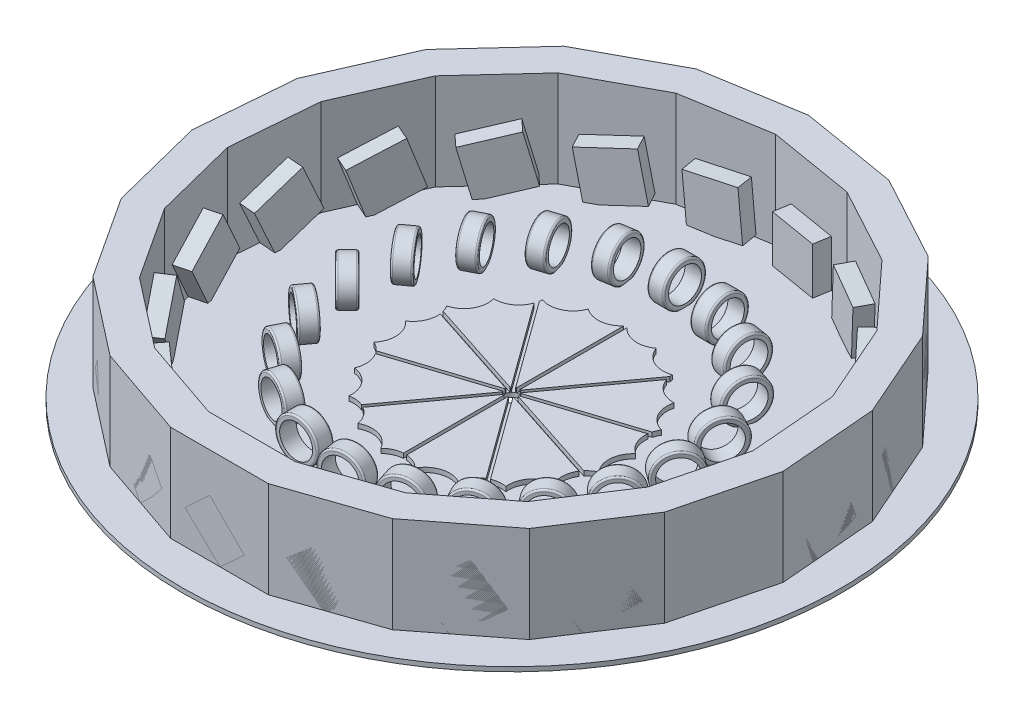
SolidWorks part; units mm, degrees
ref_plane "Front Plane" through (0, 0, 0) normal (0, 0, 1) x (1, 0, 0)
ref_plane "Top Plane" through (0, 0, 0) normal (0, 1, 0) x (1, 0, 0)
ref_plane "Right Plane" through (0, 0, 0) normal (1, 0, 0) x (0, 0, -1)
sketch "Sketch1" plane through (0, 0, 0) normal (0, 1, 0) x (1, 0, 0)
  circle A0 centre (0, 0) radius 100
  circle A1 centre (0, 0) radius 2
  dimension "D1" = 200
  dimension "D2" = 4
extrude "Base Platter" add sketch "Sketch1" along normal blind 0.75
sketch "Sketch2" plane through (0, 0.75, 0) normal (0, 1, 0) x (1, 0, 0)
  line L0 (0, 0) -> (0, 35) construction
  line L1 (0, 0) -> (10.3164, 33.445) construction
  line L2 (0, 0) -> (19.7162, 28.9184) construction
  line L3 (0, 0) -> (27.3641, 21.8221) construction
  line L4 (0, 0) -> (32.5806, 12.7869) construction
  line L5 (0, 0) -> (34.9021, 2.6156) construction
  line L6 (0, 0) -> (34.1225, -7.7882) construction
  line L7 (0, 0) -> (30.3109, -17.5) construction
  line L8 (0, 0) -> (23.806, -25.6568) construction
  line L9 (0, 0) -> (15.1859, -31.5339) construction
  line L10 (0, 0) -> (5.2165, -34.6091) construction
  line L11 (0, 0) -> (-5.2165, -34.6091) construction
  line L12 (0, 0) -> (-15.1859, -31.5339) construction
  line L13 (0, 0) -> (-23.806, -25.6568) construction
  line L14 (0, 0) -> (-30.3109, -17.5) construction
  line L15 (0, 0) -> (-34.1225, -7.7882) construction
  line L16 (0, 0) -> (-34.9021, 2.6156) construction
  line L17 (0, 0) -> (-32.5806, 12.7869) construction
  line L18 (0, 0) -> (-27.3641, 21.8221) construction
  line L19 (0, 0) -> (-19.7162, 28.9184) construction
  line L20 (0, 0) -> (-10.3164, 33.445) construction
  line L21 (0, 0) -> (4.4705, 29.665) construction
  line L22 (0, 0) -> (13.0158, 27.0294) construction
  line L23 (0, 0) -> (20.4046, 21.9921) construction
  line L24 (0, 0) -> (25.9804, 15.0006) construction
  line L25 (0, 0) -> (29.2477, 6.6764) construction
  line L26 (0, 0) -> (29.9162, -2.2412) construction
  line L27 (0, 0) -> (27.9265, -10.9595) construction
  line L28 (0, 0) -> (23.4554, -18.7041) construction
  line L29 (0, 0) -> (16.9002, -24.7867) construction
  line L30 (0, 0) -> (8.8434, -28.667) construction
  line L31 (0, 0) -> (0.0007, -30) construction
  line L32 (0, 0) -> (-8.8419, -28.6674) construction
  line L33 (0, 0) -> (-16.899, -24.7876) construction
  line L34 (0, 0) -> (-23.4545, -18.7053) construction
  line L35 (0, 0) -> (-27.9259, -10.9609) construction
  line L36 (0, 0) -> (-29.9161, -2.2426) construction
  line L37 (0, 0) -> (-29.248, 6.6749) construction
  line L38 (0, 0) -> (-25.9811, 14.9994) construction
  line L39 (0, 0) -> (-20.4057, 21.991) construction
  line L40 (0, 0) -> (-13.0172, 27.0287) construction
  line L41 (0, 0) -> (-4.472, 29.6648) construction
  line L42 (0, 0) -> (0, 59.7258) construction
  line L43 (34.5674, 11.7574) -> (-41.5171, -12.964)
  line L44 (-0.5, 36.5088) -> (0.5, 36.5088)
  line L45 (-0.5, 36.5088) -> (-0.5, -43.4912)
  line L46 (-0.5, -43.4912) -> (0.5, -43.4912)
  line L47 (0.5, 36.5088) -> (0.5, -43.4912)
  line L48 (34.8764, 10.8063) -> (-41.2081, -13.9151)
  line L49 (34.5674, 11.7574) -> (34.8764, 10.8063)
  line L50 (-41.5171, -12.964) -> (-41.2081, -13.9151)
  line L51 (21.8638, -29.2423) -> (-25.159, 35.479)
  line L52 (21.0548, -29.8301) -> (-25.968, 34.8913)
  line L53 (21.8638, -29.2423) -> (21.0548, -29.8301)
  line L54 (-25.159, 35.479) -> (-25.968, 34.8913)
  line L55 (-21.0548, -29.8301) -> (25.968, 34.8913)
  line L56 (-21.8638, -29.2423) -> (25.159, 35.479)
  line L57 (-21.0548, -29.8301) -> (-21.8638, -29.2423)
  line L58 (25.968, 34.8913) -> (25.159, 35.479)
  line L59 (-34.8764, 10.8063) -> (41.2081, -13.9151)
  line L60 (-34.5674, 11.7574) -> (41.5171, -12.964)
  line L61 (-34.8764, 10.8063) -> (-34.5674, 11.7574)
  line L62 (41.2081, -13.9151) -> (41.5171, -12.964)
  circle A0 centre (0, 0) radius 30 construction
  circle A1 centre (0, 0) radius 2 construction
  circle A2 centre (0, 0) radius 35 construction
  arc A3 (-19.7162, 28.9184) -> (-10.3164, 33.445) centre (-17.2797, 35.8816) ccw
  arc A4 (-10.3164, 33.445) -> (0, 35) centre (-5.9357, 39.3807) ccw
  arc A5 (0, 35) -> (10.3164, 33.445) centre (5.9357, 39.3807) ccw
  arc A6 (10.3164, 33.445) -> (19.7162, 28.9184) centre (17.2797, 35.8816) ccw
  arc A7 (19.7162, 28.9184) -> (27.3641, 21.8221) centre (27.0883, 29.1942) ccw
  arc A8 (27.3641, 21.8221) -> (32.5806, 12.7869) centre (34.4899, 19.9128) ccw
  arc A9 (32.5806, 12.7869) -> (34.9021, 2.6156) centre (38.827, 8.862) ccw
  arc A10 (34.9021, 2.6156) -> (34.1225, -7.7882) centre (39.7142, -2.9762) ccw
  arc A11 (34.1225, -7.7882) -> (30.3109, -17.5) centre (37.0726, -14.5499) ccw
  arc A12 (30.3109, -17.5) -> (23.806, -25.6568) centre (31.1369, -24.8308) ccw
  arc A13 (23.806, -25.6568) -> (15.1859, -31.5339) centre (22.4345, -32.9054) ccw
  arc A14 (15.1859, -31.5339) -> (5.2165, -34.6091) centre (11.7388, -38.0562) ccw
  arc A15 (5.2165, -34.6091) -> (-5.2165, -34.6091) centre (0, -39.8256) ccw
  arc A16 (-5.2165, -34.6091) -> (-15.1859, -31.5339) centre (-11.7388, -38.0562) ccw
  arc A17 (-15.1859, -31.5339) -> (-23.806, -25.6568) centre (-22.4345, -32.9054) ccw
  arc A18 (-23.806, -25.6568) -> (-30.3109, -17.5) centre (-31.1369, -24.8308) ccw
  arc A19 (-30.3109, -17.5) -> (-34.1225, -7.7882) centre (-37.0726, -14.5499) ccw
  arc A20 (-34.1225, -7.7882) -> (-34.9021, 2.6156) centre (-39.7142, -2.9762) ccw
  arc A21 (-34.9021, 2.6156) -> (-32.5806, 12.7869) centre (-38.827, 8.862) ccw
  arc A22 (-32.5806, 12.7869) -> (-27.3641, 21.8221) centre (-34.4899, 19.9128) ccw
  arc A23 (-27.3641, 21.8221) -> (-19.7162, 28.9184) centre (-27.0883, 29.1942) ccw
  circle A24 centre (0, 0) radius 2
  point P28 (0, 0)
  point P50 (0, 0)
  point P65 (0, 36.5088)
  point P112 (0, 0)
  point P116 (0, 0)
  dimension "D1" = 60
  dimension "D2" = 70
  dimension "D7" = 4
  dimension "D4" = 8.57
  dimension "D8" = 80
  dimension "D9" = 1
  dimension "D3" = 21
  dimension "D5" = 21
  dimension "D6" = 21
  dimension "D10" = 5
extrude "Inner Design" add sketch "Sketch2" along normal blind 2 contours A23 A22 A21 L60 L52 | A21 A20 A19 L43 L59 | A19 A18 A17 L56 L48 | A17 A16 A15 L45 L55 | A15 A14 A13 L52 L47 | A13 A12 A11 L59 L51 | A11 A10 A9 L48 L60 | A9 A8 A7 L55 L43 | A6 A5 L47 L56 | A4 A3 L51 L45 region at (18.1502, 0.75, -13.0736) region at (22.3712, 0.75, 0.0918) region at (6.9566, 0.75, -21.2572) region at (18.0627, 0.75, 13.2035) region at (-6.9566, 0.75, -21.2572) region at (6.8923, 0.75, 21.2873) region at (-18.1502, 0.75, -13.0736) region at (-6.8923, 0.75, 21.2873) region at (-22.3712, 0.75, 0.0918) region at (-18.0627, 0.75, 13.2035)
sketch "Sketch3" plane through (0, 0.75, 0) normal (0, 1, 0) x (1, 0, 0)
  line L1 (0, 90) -> (-29.223, 85.1236)
  line L2 (-29.223, 85.1236) -> (-55.2791, 71.0226)
  line L3 (-55.2791, 71.0226) -> (-75.345, 49.2253)
  line L4 (-75.345, 49.2253) -> (-87.246, 22.0937)
  line L5 (-87.246, 22.0937) -> (-89.6926, -7.4321)
  line L6 (-89.6926, -7.4321) -> (-82.4196, -36.1526)
  line L7 (-82.4196, -36.1526) -> (-66.2152, -60.9553)
  line L8 (-66.2152, -60.9553) -> (-42.8353, -79.1526)
  line L9 (-42.8353, -79.1526) -> (-14.8135, -88.7725)
  line L10 (-14.8135, -88.7725) -> (14.8135, -88.7725)
  line L11 (14.8135, -88.7725) -> (42.8353, -79.1526)
  line L12 (42.8353, -79.1526) -> (66.2152, -60.9553)
  line L13 (66.2152, -60.9553) -> (82.4196, -36.1526)
  line L14 (82.4196, -36.1526) -> (89.6926, -7.4321)
  line L15 (89.6926, -7.4321) -> (87.246, 22.0937)
  line L16 (87.246, 22.0937) -> (75.345, 49.2253)
  line L17 (75.345, 49.2253) -> (55.2791, 71.0226)
  line L18 (55.2791, 71.0226) -> (29.223, 85.1236)
  line L19 (29.223, 85.1236) -> (0, 90)
  line L20 (0, 80) -> (-25.976, 75.6654)
  line L21 (-25.976, 75.6654) -> (-49.137, 63.1312)
  line L22 (-49.137, 63.1312) -> (-66.9733, 43.7559)
  line L23 (-66.9733, 43.7559) -> (-77.552, 19.6388)
  line L24 (-77.552, 19.6388) -> (-79.7268, -6.6063)
  line L25 (-79.7268, -6.6063) -> (-73.2619, -32.1356)
  line L26 (-73.2619, -32.1356) -> (-58.8579, -54.1825)
  line L27 (-58.8579, -54.1825) -> (-38.0758, -70.3579)
  line L28 (-38.0758, -70.3579) -> (-13.1676, -78.9089)
  line L29 (-13.1676, -78.9089) -> (13.1676, -78.9089)
  line L30 (13.1676, -78.9089) -> (38.0758, -70.3579)
  line L31 (38.0758, -70.3579) -> (58.8579, -54.1825)
  line L32 (58.8579, -54.1825) -> (73.2619, -32.1356)
  line L33 (73.2619, -32.1356) -> (79.7268, -6.6063)
  line L34 (79.7268, -6.6063) -> (77.552, 19.6388)
  line L35 (77.552, 19.6388) -> (66.9733, 43.7559)
  line L36 (66.9733, 43.7559) -> (49.137, 63.1312)
  line L37 (49.137, 63.1312) -> (25.976, 75.6654)
  line L38 (25.976, 75.6654) -> (0, 80)
  circle A0 centre (0, 0) radius 90 construction
  circle A1 centre (0, 0) radius 80 construction
  circle A2 centre (0, 0) radius 88.7725 construction
  circle A3 centre (0, 0) radius 78.9089 construction
  dimension "D1" = 180
  dimension "D2" = 160
extrude "Cube Face Reference" add sketch "Sketch3" along normal blind 29.8 separate body
sketch "Sketch4" plane through (14.6115, 0, -87.5618) normal (0.1646, 0, -0.9864) x (-0.9864, 0, -0.1646)
  line L0 (0, 0.75) -> (0, 30.55) construction
  line L1 (100, 0.75) -> (-100, 0.75) construction
  line L2 (-14.8135, 30.55) -> (14.8135, 30.55) construction
  line L3 (-14.8135, 0.75) -> (14.8135, 0.75) construction
  line L4 (-7.4075, 0.75) -> (7.4075, 0.75)
  line L5 (-7.4075, 0.75) -> (-7.4075, 15.57)
  line L6 (-7.4075, 15.57) -> (7.4075, 15.57)
  line L7 (7.4075, 0.75) -> (7.4075, 15.57)
  point P12 (0, 15.57)
  dimension "D1" = 14.815
  dimension "D2" = 14.82
extrude "First Cube" add sketch "Sketch4" against normal blind 14.82 separate body
sketch "Sketch5" plane through (42.251, 0, -78.0731) normal (0.4759, 0, -0.8795) x (-0.8795, 0, -0.4759)
  line L0 (-6.7728, 0.75) -> (7.9966, 1.9738)
  line L1 (-14.8135, 0.75) -> (14.8135, 0.75) construction
  line L2 (7.9966, 1.9738) -> (6.7728, 16.7432)
  line L3 (6.7728, 16.7432) -> (-7.9966, 15.5194)
  line L4 (-7.9966, 15.5194) -> (-6.7728, 0.75)
  line L5 (6.7728, 16.7432) -> (-6.7728, 0.75) construction
  line L6 (7.9966, 1.9738) -> (-7.9966, 15.5194) construction
  line L7 (100, 0.75) -> (-100, 0.75) construction
  line L8 (-14.8135, 30.55) -> (14.8135, 30.55) construction
  point P4 (0, 0)
  point P11 (0, 30.55)
  point P12 (0, 8.7466)
  dimension "D1" = 14.82
  dimension "D2" = 14.82
  dimension "D3" = 4.737
extrude "Boss-Extrude6" add sketch "Sketch5" against normal blind 14.82 separate body
sketch "Sketch6" plane through (65.3121, 0, -60.124) normal (0.7357, 0, -0.6773) x (-0.6773, 0, -0.7357)
  line L0 (-6.0893, 0.75) -> (-8.5286, 15.3679)
  line L1 (-14.8135, 0.75) -> (14.8135, 0.75) construction
  line L2 (-8.5286, 15.3679) -> (6.0893, 17.8072)
  line L3 (6.0893, 17.8072) -> (8.5286, 3.1893)
  line L4 (8.5286, 3.1893) -> (-6.0893, 0.75)
  line L5 (6.0893, 17.8072) -> (-6.0893, 0.75) construction
  line L6 (-8.5286, 15.3679) -> (8.5286, 3.1893) construction
  point P4 (0, 9.2786)
  dimension "D1" = 14.82
  dimension "D2" = 14.82
  dimension "D3" = 9.474
extrude "Boss-Extrude7" add sketch "Sketch6" against normal blind 14.82 separate body
sketch "Sketch7" plane through (81.2955, 0, -35.6595) normal (0.9158, 0, -0.4017) x (-0.4017, 0, -0.9158)
  line L0 (-5.3642, 0.75) -> (-9.0023, 15.1165)
  line L2 (-9.0023, 15.1165) -> (5.3642, 18.7546)
  line L3 (5.3642, 18.7546) -> (9.0023, 4.3881)
  line L4 (9.0023, 4.3881) -> (-5.3642, 0.75)
  line L5 (5.3642, 18.7546) -> (-5.3642, 0.75) construction
  line L6 (9.0023, 4.3881) -> (-9.0023, 15.1165) construction
  line L7 (100, 0.75) -> (-100, 0.75) construction
  line L8 (-14.8135, 0.75) -> (14.8135, 0.75) construction
  point P2 (0, 0)
  point P4 (0, 9.7523)
  dimension "D1" = 14.82
  dimension "D2" = 14.82
  dimension "D3" = 14.211
extrude "Boss-Extrude9" add sketch "Sketch7" against normal blind 14.82 separate body
sketch "Sketch8" plane through (88.4693, 0, -7.3308) normal (0.9966, 0, -0.0826) x (-0.0826, 0, -0.9966)
  line L0 (-4.6025, 0.75) -> (-9.4145, 14.767)
  line L2 (-9.4145, 14.767) -> (4.6025, 19.5791)
  line L3 (4.6025, 19.5791) -> (9.4145, 5.562)
  line L4 (9.4145, 5.562) -> (-4.6025, 0.75)
  line L5 (-14.8135, 0.75) -> (14.8135, 0.75) construction
  line L6 (-4.6025, 0.75) -> (4.6025, 19.5791) construction
  line L7 (9.4145, 5.562) -> (-9.4145, 14.767) construction
  line L8 (-14.8135, 30.55) -> (14.8135, 30.55) construction
  point P8 (0, 30.55)
  point P9 (0, 10.1645)
  dimension "D1" = 14.82
  dimension "D2" = 14.82
  dimension "D3" = 18.947
extrude "Boss-Extrude10" add sketch "Sketch8" against normal blind 14.82 separate body
sketch "Sketch9" plane through (86.0561, 0, 21.7924) normal (0.9694, 0, 0.2455) x (0.2455, 0, -0.9694)
  line L0 (-3.8093, 0.75) -> (-9.7624, 14.3218)
  line L1 (-14.8135, 0.75) -> (14.8135, 0.75) construction
  line L2 (-9.7624, 14.3218) -> (3.8093, 20.2749)
  line L3 (3.8093, 20.2749) -> (9.7624, 6.7031)
  line L4 (9.7624, 6.7031) -> (-3.8093, 0.75)
  line L5 (-3.8093, 0.75) -> (3.8093, 20.2749)
  line L6 (9.7624, 6.7031) -> (-9.7624, 14.3218)
  point P4 (0, 10.5124)
  dimension "D1" = 14.82
  dimension "D2" = 14.82
  dimension "D3" = 23.684
extrude "Boss-Extrude11" add sketch "Sketch9" against normal blind 14.82 separate body contours L6 L5 L2 | L6 L3 L5 | L4 L6 L5 | L5 L6 L0 region at (86.5432, 5.9885, 19.8687) region at (84.9455, 8.5281, 26.1779) region at (85.569, 15.0364, 23.716) region at (87.1667, 12.4968, 17.4069)
sketch "Sketch10" plane through (74.3174, 0, 48.554) normal (0.8372, 0, 0.5469) x (0.5469, 0, -0.8372)
  line L0 (-2.9901, 0.75) -> (-10.0437, 13.7838)
  line L1 (-14.8135, 0.75) -> (14.8135, 0.75) construction
  line L2 (-10.0437, 13.7838) -> (2.9901, 20.8373)
  line L3 (2.9901, 20.8373) -> (10.0437, 7.8035)
  line L4 (10.0437, 7.8035) -> (-2.9901, 0.75)
  line L5 (-2.9901, 0.75) -> (2.9901, 20.8373) construction
  line L6 (10.0437, 7.8035) -> (-10.0437, 13.7838) construction
  point P4 (0, 0.75)
  point P7 (0, 10.7937)
  dimension "D1" = 14.82
  dimension "D2" = 14.82
  dimension "D3" = 28.421
extrude "Boss-Extrude12" add sketch "Sketch10" against normal blind 14.82 separate body
sketch "Sketch11" plane through (54.5252, 0, 70.054) normal (0.6142, 0, 0.7891) x (0.7891, 0, -0.6142)
  line L0 (-2.1505, 0.75) -> (-10.2563, 13.1568)
  line L1 (-14.8135, 0.75) -> (14.8135, 0.75) construction
  line L2 (-10.2563, 13.1568) -> (2.1505, 21.2626)
  line L3 (2.1505, 21.2626) -> (10.2563, 8.8558)
  line L4 (10.2563, 8.8558) -> (-2.1505, 0.75)
  line L5 (2.1505, 21.2626) -> (-2.1505, 0.75) construction
  line L6 (10.2563, 8.8558) -> (-10.2563, 13.1568) construction
  line L7 (-14.8135, 30.55) -> (14.8135, 30.55) construction
  line L8 (100, 0.75) -> (-100, 0.75) construction
  point P8 (0, 30.55)
  point P9 (0, 11.0063)
  dimension "D1" = 14.82
  dimension "D2" = 14.82
  dimension "D3" = 33.158
extrude "Boss-Extrude14" add sketch "Sketch11" against normal blind 14.82 separate body
sketch "Sketch12" plane through (28.8244, 0, 83.9626) normal (0.3247, 0, 0.9458) x (0.9458, 0, -0.3247)
  line L0 (-1.2962, 0.75) -> (-10.3988, 12.4451)
  line L1 (100, 0.75) -> (-100, 0.75) construction
  line L2 (-10.3988, 12.4451) -> (1.2962, 21.5477)
  line L3 (1.2962, 21.5477) -> (10.3988, 9.8526)
  line L4 (10.3988, 9.8526) -> (-1.2962, 0.75)
  line L5 (1.2962, 21.5477) -> (-1.2962, 0.75) construction
  line L6 (-10.3988, 12.4451) -> (10.3988, 9.8526) construction
  line L7 (-14.8135, 30.55) -> (14.8135, 30.55) construction
  line L8 (-14.8135, 0.75) -> (14.8135, 0.75) construction
  point P8 (0, 30.55)
  point P9 (0, 11.1488)
  dimension "D1" = 14.82
  dimension "D2" = 14.82
  dimension "D3" = 37.895
extrude "Boss-Extrude15" add sketch "Sketch12" against normal blind 14.82 separate body
sketch "Sketch13" plane through (0, 0, 88.7725) normal (0, 0, 1) x (1, 0, 0)
  line L0 (-0.4331, 0.75) -> (-10.4704, 11.6534)
  line L1 (-14.8135, 0.75) -> (14.8135, 0.75) construction
  line L2 (-10.4704, 11.6534) -> (0.4331, 21.6907)
  line L3 (0.4331, 21.6907) -> (10.4704, 10.7873)
  line L4 (10.4704, 10.7873) -> (-0.4331, 0.75)
  line L5 (0.4331, 21.6907) -> (-0.4331, 0.75) construction
  line L6 (-10.4704, 11.6534) -> (10.4704, 10.7873) construction
  line L7 (100, 0.75) -> (-100, 0.75) construction
  point P8 (0, 0.75)
  point P9 (0, 11.2204)
  dimension "D1" = 14.82
  dimension "D2" = 14.82
  dimension "D3" = 42.632
extrude "Boss-Extrude16" add sketch "Sketch13" against normal blind 14.82 separate body
sketch "Sketch14" plane through (-28.8244, 0, 83.9626) normal (-0.3247, 0, 0.9458) x (0.9458, 0, 0.3247)
  line L0 (0.4331, 0.75) -> (-10.4704, 10.7873)
  line L1 (100, 0.75) -> (-100, 0.75) construction
  line L2 (-10.4704, 10.7873) -> (-0.4331, 21.6907)
  line L3 (-0.4331, 21.6907) -> (10.4704, 11.6534)
  line L4 (10.4704, 11.6534) -> (0.4331, 0.75)
  line L5 (0.4331, 0.75) -> (-0.4331, 21.6907) construction
  line L6 (-10.4704, 10.7873) -> (10.4704, 11.6534) construction
  line L7 (-14.8135, 0.75) -> (14.8135, 0.75) construction
  point P4 (0, 11.2204)
  dimension "D1" = 14.82
  dimension "D2" = 14.82
  dimension "D3" = 47.368
extrude "Boss-Extrude18" add sketch "Sketch14" against normal blind 14.82 separate body
sketch "Sketch15" plane through (-54.5252, 0, 70.054) normal (-0.6142, 0, 0.7891) x (0.7891, 0, 0.6142)
  line L0 (1.2962, 0.75) -> (-10.3988, 9.8526)
  line L1 (-14.8135, 0.75) -> (14.8135, 0.75) construction
  line L2 (-10.3988, 9.8526) -> (-1.2962, 21.5477)
  line L3 (-1.2962, 21.5477) -> (10.3988, 12.4451)
  line L4 (10.3988, 12.4451) -> (1.2962, 0.75)
  line L5 (1.2962, 0.75) -> (-1.2962, 21.5477) construction
  line L6 (10.3988, 12.4451) -> (-10.3988, 9.8526) construction
  line L7 (-14.8135, 30.55) -> (14.8135, 30.55) construction
  line L8 (100, 0.75) -> (-100, 0.75) construction
  point P8 (0, 30.55)
  point P9 (0, 11.1488)
  dimension "D1" = 14.82
  dimension "D2" = 14.82
  dimension "D3" = 52.105
extrude "Boss-Extrude19" add sketch "Sketch15" against normal blind 14.82 separate body
sketch "Sketch16" plane through (-74.3174, 0, 48.554) normal (-0.8372, 0, 0.5469) x (0.5469, 0, 0.8372)
  line L0 (2.1505, 0.75) -> (-10.2563, 8.8558)
  line L1 (-14.8135, 0.75) -> (14.8135, 0.75) construction
  line L2 (-10.2563, 8.8558) -> (-2.1505, 21.2626)
  line L3 (-2.1505, 21.2626) -> (10.2563, 13.1568)
  line L4 (10.2563, 13.1568) -> (2.1505, 0.75)
  line L5 (2.1505, 0.75) -> (-2.1505, 21.2626) construction
  line L6 (10.2563, 13.1568) -> (-10.2563, 8.8558) construction
  line L7 (-14.8135, 30.55) -> (14.8135, 30.55) construction
  point P8 (0, 30.55)
  point P9 (0, 11.0063)
  dimension "D1" = 14.82
  dimension "D2" = 14.82
  dimension "D3" = 56.842
extrude "Boss-Extrude20" add sketch "Sketch16" against normal blind 14.82 separate body
sketch "Sketch17" plane through (-86.0561, 0, 21.7924) normal (-0.9694, 0, 0.2455) x (0.2455, 0, 0.9694)
  line L0 (2.9901, 0.75) -> (-10.0437, 7.8035)
  line L1 (100, 0.75) -> (-100, 0.75) construction
  line L2 (-10.0437, 7.8035) -> (-2.9901, 20.8373)
  line L3 (-2.9901, 20.8373) -> (10.0437, 13.7838)
  line L4 (10.0437, 13.7838) -> (2.9901, 0.75)
  line L5 (2.9901, 0.75) -> (-2.9901, 20.8373) construction
  line L6 (10.0437, 13.7838) -> (-10.0437, 7.8035) construction
  line L7 (-14.8135, 30.55) -> (14.8135, 30.55) construction
  line L8 (-14.8135, 0.75) -> (14.8135, 0.75) construction
  point P8 (0, 30.55)
  point P9 (0, 10.7937)
  dimension "D1" = 14.82
  dimension "D2" = 14.82
  dimension "D3" = 14.82
  dimension "D4" = 61.579
extrude "Boss-Extrude21" add sketch "Sketch17" against normal blind 14.82 separate body
sketch "Sketch18" plane through (-88.4693, 0, -7.3308) normal (-0.9966, 0, -0.0826) x (-0.0826, 0, 0.9966)
  line L0 (3.8093, 0.75) -> (-9.7624, 6.7031)
  line L1 (100, 0.75) -> (-100, 0.75) construction
  line L2 (-9.7624, 6.7031) -> (-3.8093, 20.2749)
  line L3 (-3.8093, 20.2749) -> (9.7624, 14.3218)
  line L4 (9.7624, 14.3218) -> (3.8093, 0.75)
  line L5 (-3.8093, 20.2749) -> (3.8093, 0.75) construction
  line L6 (9.7624, 14.3218) -> (-9.7624, 6.7031) construction
  line L7 (-14.8135, 30.55) -> (14.8135, 30.55) construction
  line L8 (-14.8135, 0.75) -> (14.8135, 0.75) construction
  point P8 (0, 30.55)
  point P9 (0, 10.5124)
  dimension "D1" = 14.82
  dimension "D2" = 14.82
  dimension "D3" = 66.316
extrude "Boss-Extrude23" add sketch "Sketch18" against normal blind 14.82 separate body
sketch "Sketch19" plane through (-81.2955, 0, -35.6595) normal (-0.9158, 0, -0.4017) x (-0.4017, 0, 0.9158)
  line L0 (4.6025, 0.75) -> (-9.4145, 5.562)
  line L1 (-14.8135, 0.75) -> (14.8135, 0.75) construction
  line L2 (-9.4145, 5.562) -> (-4.6025, 19.5791)
  line L3 (-4.6025, 19.5791) -> (9.4145, 14.767)
  line L4 (9.4145, 14.767) -> (4.6025, 0.75)
  line L5 (4.6025, 0.75) -> (-4.6025, 19.5791) construction
  line L6 (9.4145, 14.767) -> (-9.4145, 5.562) construction
  line L7 (-14.8135, 30.55) -> (14.8135, 30.55) construction
  point P8 (0, 30.55)
  point P9 (0, 10.1645)
  dimension "D1" = 14.82
  dimension "D2" = 14.82
  dimension "D3" = 71.053
extrude "Boss-Extrude24" add sketch "Sketch19" against normal blind 14.82 separate body
sketch "Sketch20" plane through (-65.3121, 0, -60.124) normal (-0.7357, 0, -0.6773) x (-0.6773, 0, 0.7357)
  line L0 (5.3642, 0.75) -> (-9.0023, 4.3881)
  line L1 (100, 0.75) -> (-100, 0.75) construction
  line L2 (-9.0023, 4.3881) -> (-5.3642, 18.7546)
  line L3 (-5.3642, 18.7546) -> (9.0023, 15.1165)
  line L4 (9.0023, 15.1165) -> (5.3642, 0.75)
  line L5 (-5.3642, 18.7546) -> (5.3642, 0.75) construction
  line L6 (9.0023, 15.1165) -> (-9.0023, 4.3881) construction
  line L7 (-14.8135, 30.55) -> (14.8135, 30.55) construction
  point P8 (0, 30.55)
  point P9 (0, 9.7523)
  dimension "D1" = 14.82
  dimension "D2" = 14.82
  dimension "D3" = 75.789
extrude "Boss-Extrude25" add sketch "Sketch20" against normal blind 14.82 separate body
sketch "Sketch21" plane through (-42.251, 0, -78.0731) normal (-0.4759, 0, -0.8795) x (-0.8795, 0, 0.4759)
  line L0 (6.0893, 0.75) -> (-8.5286, 3.1893)
  line L1 (-14.8135, 0.75) -> (14.8135, 0.75) construction
  line L2 (-8.5286, 3.1893) -> (-6.0893, 17.8072)
  line L3 (-6.0893, 17.8072) -> (8.5286, 15.3679)
  line L4 (8.5286, 15.3679) -> (6.0893, 0.75)
  line L5 (6.0893, 0.75) -> (-6.0893, 17.8072) construction
  line L6 (8.5286, 15.3679) -> (-8.5286, 3.1893) construction
  line L7 (-14.8135, 30.55) -> (14.8135, 30.55) construction
  point P8 (0, 30.55)
  point P9 (0, 9.2786)
  dimension "D1" = 14.82
  dimension "D2" = 14.82
  dimension "D3" = 80.526
extrude "Boss-Extrude26" add sketch "Sketch21" against normal blind 14.82 separate body
sketch "Sketch22" plane through (-14.6115, 0, -87.5618) normal (-0.1646, 0, -0.9864) x (-0.9864, 0, 0.1646)
  line L0 (6.7728, 0.75) -> (-7.9966, 1.9738)
  line L1 (-14.8135, 0.75) -> (14.8135, 0.75) construction
  line L2 (-7.9966, 1.9738) -> (-6.7728, 16.7432)
  line L3 (-6.7728, 16.7432) -> (7.9966, 15.5194)
  line L4 (7.9966, 15.5194) -> (6.7728, 0.75)
  line L5 (6.7728, 0.75) -> (-6.7728, 16.7432) construction
  line L6 (-7.9966, 1.9738) -> (7.9966, 15.5194) construction
  line L7 (100, 0.75) -> (-100, 0.75) construction
  point P4 (0, 8.7466)
  dimension "D1" = 14.82
  dimension "D2" = 14.82
  dimension "D3" = 85.263
extrude "Boss-Extrude27" add sketch "Sketch22" against normal blind 14.82 separate body
sketch "Sketch23" plane through (0, 0.75, 0) normal (0, 1, 0) x (1, 0, 0)
  line L0 (0, 0) -> (0, 50) construction
  line L1 (0, 0) -> (15.4508, 47.5528) construction
  line L6 (0, 0) -> (29.3893, 40.4508) construction
  line L7 (0, 0) -> (40.4508, 29.3893) construction
  line L8 (0, 0) -> (47.5528, 15.4508) construction
  line L9 (0, 0) -> (50, 0) construction
  line L10 (0, 0) -> (47.5528, -15.4508) construction
  line L11 (0, 0) -> (40.4508, -29.3893) construction
  line L12 (0, 0) -> (29.3893, -40.4508) construction
  line L13 (0, 0) -> (15.4508, -47.5528) construction
  line L14 (0, 0) -> (0, -50) construction
  line L15 (0, 0) -> (-15.4508, -47.5528) construction
  line L16 (0, 0) -> (-29.3893, -40.4508) construction
  line L17 (0, 0) -> (-40.4508, -29.3893) construction
  line L18 (0, 0) -> (-47.5528, -15.4508) construction
  line L19 (0, 0) -> (-50, 0) construction
  line L20 (0, 0) -> (-47.5528, 15.4508) construction
  line L21 (0, 0) -> (-40.4508, 29.3893) construction
  line L22 (0, 0) -> (-29.3893, 40.4508) construction
  line L23 (0, 0) -> (-15.4508, 47.5528) construction
  line L24 (12.9508, 54.0528) -> (12.9508, 41.0528)
  line L25 (-2.5, 56.5) -> (2.5, 56.5)
  line L26 (-2.5, 56.5) -> (-2.5, 43.5)
  line L27 (-2.5, 43.5) -> (2.5, 43.5)
  line L28 (2.5, 56.5) -> (2.5, 43.5)
  line L29 (12.9508, 41.0528) -> (17.9508, 41.0528)
  line L30 (17.9508, 41.0528) -> (17.9508, 54.0528)
  line L31 (17.9508, 54.0528) -> (12.9508, 54.0528)
  line L32 (12.9508, 41.0528) -> (17.9508, 54.0528) construction
  line L33 (17.9508, 41.0528) -> (12.9508, 54.0528) construction
  line L34 (27.9369, 47.2619) -> (32.8753, 46.4797)
  line L35 (32.8753, 46.4797) -> (30.8417, 33.6398)
  line L36 (30.8417, 33.6398) -> (25.9032, 34.422)
  line L37 (25.9032, 34.422) -> (27.9369, 47.2619)
  line L38 (25.9032, 34.422) -> (32.8753, 46.4797) construction
  line L39 (30.8417, 33.6398) -> (27.9369, 47.2619) construction
  line L40 (40.0818, 36.3437) -> (36.0646, 23.9799)
  line L41 (36.0646, 23.9799) -> (40.8199, 22.4349)
  line L42 (40.8199, 22.4349) -> (44.8371, 34.7986)
  line L43 (44.8371, 34.7986) -> (40.0818, 36.3437)
  line L44 (40.8199, 22.4349) -> (40.0818, 36.3437) construction
  line L45 (44.8371, 34.7986) -> (36.0646, 23.9799) construction
  line L46 (48.2762, 22.3774) -> (42.3744, 10.7943)
  line L47 (42.3744, 10.7943) -> (46.8294, 8.5243)
  line L48 (46.8294, 8.5243) -> (52.7313, 20.1074)
  line L49 (52.7313, 20.1074) -> (48.2762, 22.3774)
  line L50 (46.8294, 8.5243) -> (48.2762, 22.3774) construction
  line L51 (52.7313, 20.1074) -> (42.3744, 10.7943) construction
  line L52 (51.7981, 6.7281) -> (44.1569, -3.7891)
  line L53 (44.1569, -3.7891) -> (48.2019, -6.7281)
  line L54 (48.2019, -6.7281) -> (55.8431, 3.7891)
  line L55 (55.8431, 3.7891) -> (51.7981, 6.7281)
  line L56 (48.2019, -6.7281) -> (51.7981, 6.7281) construction
  line L57 (55.8431, 3.7891) -> (44.1569, -3.7891) construction
  line L58 (50.3813, -9.0869) -> (41.1889, -18.2793)
  line L59 (41.1889, -18.2793) -> (44.7244, -21.8148)
  line L60 (44.7244, -21.8148) -> (53.9168, -12.6224)
  line L61 (53.9168, -12.6224) -> (50.3813, -9.0869)
  line L62 (44.7244, -21.8148) -> (50.3813, -9.0869) construction
  line L63 (53.9168, -12.6224) -> (41.1889, -18.2793) construction
  line L64 (44.24, -23.5461) -> (33.7228, -31.1873)
  line L65 (33.7228, -31.1873) -> (36.6617, -35.2324)
  line L66 (36.6617, -35.2324) -> (47.1789, -27.5912)
  line L67 (47.1789, -27.5912) -> (44.24, -23.5461)
  line L68 (36.6617, -35.2324) -> (44.24, -23.5461) construction
  line L69 (47.1789, -27.5912) -> (33.7228, -31.1873) construction
  line L70 (24.7327, -45.6293) -> (36.3158, -39.7274)
  line L71 (36.3158, -39.7274) -> (34.0458, -35.2724)
  line L72 (34.0458, -35.2724) -> (22.4627, -41.1743)
  line L73 (22.4627, -41.1743) -> (24.7327, -45.6293)
  line L74 (34.0458, -35.2724) -> (24.7327, -45.6293) construction
  line L75 (22.4627, -41.1743) -> (36.3158, -39.7274) construction
  line L76 (10.0415, -51.9391) -> (22.4053, -47.9219)
  line L77 (22.4053, -47.9219) -> (20.8602, -43.1666)
  line L78 (20.8602, -43.1666) -> (8.4964, -47.1838)
  line L79 (8.4964, -47.1838) -> (10.0415, -51.9391)
  line L80 (20.8602, -43.1666) -> (10.0415, -51.9391) construction
  line L81 (8.4964, -47.1838) -> (22.4053, -47.9219) construction
  line L82 (-6.0289, -53.486) -> (6.8111, -51.4524)
  line L83 (6.8111, -51.4524) -> (6.0289, -46.514)
  line L84 (6.0289, -46.514) -> (-6.8111, -48.5476)
  line L85 (-6.8111, -48.5476) -> (-6.0289, -53.486)
  line L86 (6.0289, -46.514) -> (-6.0289, -53.486) construction
  line L87 (-6.8111, -48.5476) -> (6.8111, -51.4524) construction
  line L88 (-21.9508, -50.0528) -> (-8.9508, -50.0528)
  line L89 (-8.9508, -50.0528) -> (-8.9508, -45.0528)
  line L90 (-8.9508, -45.0528) -> (-21.9508, -45.0528)
  line L91 (-21.9508, -45.0528) -> (-21.9508, -50.0528)
  line L92 (-8.9508, -45.0528) -> (-21.9508, -50.0528) construction
  line L93 (-21.9508, -45.0528) -> (-8.9508, -50.0528) construction
  line L94 (-36.3437, -40.8199) -> (-23.9799, -44.8371)
  line L95 (-23.9799, -44.8371) -> (-22.4349, -40.0818)
  line L96 (-22.4349, -40.0818) -> (-34.7986, -36.0646)
  line L97 (-34.7986, -36.0646) -> (-36.3437, -40.8199)
  line L98 (-22.4349, -40.0818) -> (-36.3437, -40.8199) construction
  line L99 (-34.7986, -36.0646) -> (-23.9799, -44.8371) construction
  line L100 (-47.3774, -28.6658) -> (-35.7943, -34.5677)
  line L101 (-35.7943, -34.5677) -> (-33.5243, -30.1127)
  line L102 (-33.5243, -30.1127) -> (-45.1074, -24.2108)
  line L103 (-45.1074, -24.2108) -> (-47.3774, -28.6658)
  line L104 (-33.5243, -30.1127) -> (-47.3774, -28.6658) construction
  line L105 (-45.1074, -24.2108) -> (-35.7943, -34.5677) construction
  line L106 (-54.2809, -13.6528) -> (-43.7637, -21.294)
  line L107 (-43.7637, -21.294) -> (-40.8248, -17.2489)
  line L108 (-40.8248, -17.2489) -> (-51.342, -9.6077)
  line L109 (-51.342, -9.6077) -> (-54.2809, -13.6528)
  line L110 (-40.8248, -17.2489) -> (-54.2809, -13.6528) construction
  line L111 (-51.342, -9.6077) -> (-43.7637, -21.294) construction
  line L112 (-56.364, 2.8284) -> (-47.1716, -6.364)
  line L113 (-47.1716, -6.364) -> (-43.636, -2.8284)
  line L114 (-43.636, -2.8284) -> (-52.8284, 6.364)
  line L115 (-52.8284, 6.364) -> (-56.364, 2.8284)
  line L116 (-43.636, -2.8284) -> (-56.364, 2.8284) construction
  line L117 (-52.8284, 6.364) -> (-47.1716, -6.364) construction
  line L118 (-53.396, 19.24) -> (-45.7548, 8.7228)
  line L119 (-45.7548, 8.7228) -> (-41.7097, 11.6617)
  line L120 (-41.7097, 11.6617) -> (-49.3509, 22.1789)
  line L121 (-49.3509, 22.1789) -> (-53.396, 19.24)
  line L122 (-41.7097, 11.6617) -> (-53.396, 19.24) construction
  line L123 (-49.3509, 22.1789) -> (-45.7548, 8.7228) construction
  line L124 (-45.6293, 34.0458) -> (-39.7274, 22.4627)
  line L125 (-39.7274, 22.4627) -> (-35.2724, 24.7327)
  line L126 (-35.2724, 24.7327) -> (-41.1743, 36.3158)
  line L127 (-41.1743, 36.3158) -> (-45.6293, 34.0458)
  line L128 (-35.2724, 24.7327) -> (-45.6293, 34.0458) construction
  line L129 (-41.1743, 36.3158) -> (-39.7274, 22.4627) construction
  line L130 (-33.7755, 45.8602) -> (-29.7583, 33.4964)
  line L131 (-29.7583, 33.4964) -> (-25.003, 35.0415)
  line L132 (-25.003, 35.0415) -> (-29.0202, 47.4053)
  line L133 (-29.0202, 47.4053) -> (-33.7755, 45.8602)
  line L134 (-25.003, 35.0415) -> (-33.7755, 45.8602) construction
  line L135 (-29.0202, 47.4053) -> (-29.7583, 33.4964) construction
  line L136 (-18.9369, 53.5817) -> (-16.9032, 40.7418)
  line L137 (-16.9032, 40.7418) -> (-11.9648, 41.5239)
  line L138 (-11.9648, 41.5239) -> (-13.9985, 54.3639)
  line L139 (-13.9985, 54.3639) -> (-18.9369, 53.5817)
  line L140 (-11.9648, 41.5239) -> (-18.9369, 53.5817) construction
  line L141 (-13.9985, 54.3639) -> (-16.9032, 40.7418) construction
  point P25 (0, 0)
  point P27 (0, 56.5)
  point P28 (2.5, 50)
  point P31 (15.4508, 47.5528)
  point P36 (29.3893, 40.4508)
  point P47 (-47.5528, -15.4508)
  point P50 (-50, 0)
  point P51 (-47.5528, 15.4508)
  point P54 (-40.4508, 29.3893)
  point P57 (-29.3893, 40.4508)
  point P60 (0, 0)
  point P63 (-15.4508, 47.5528)
  point P69 (29.3893, -40.4508)
  point P139 (0, 0)
  point P140 (40.4508, 29.3893)
  point P141 (47.5528, 15.4508)
  point P142 (50, 0)
  point P143 (57.2575, 7.0413)
  point P144 (47.5528, -15.4508)
  point P145 (57.2085, -13.843)
  point P146 (40.4508, -29.3893)
  point P147 (50.5627, -29.3893)
  point P148 (38.8762, -43.9505)
  point P149 (15.4508, -47.5528)
  point P150 (20.6773, -56.2093)
  point P151 (0, -50)
  point P152 (8.5265, -55.4359)
  point P153 (-15.4508, -47.5528)
  point P154 (-29.3893, -40.4508)
  point P155 (-40.4508, -29.3893)
  dimension "D1" = 50
  dimension "D2" = 20
  dimension "D3" = 5
  dimension "D4" = 13
  dimension "D5" = 5
  dimension "D6" = 13
  dimension "D7" = 18
  dimension "D8" = 5
  dimension "D9" = 13
  dimension "D10" = 27
  dimension "D11" = 5
  dimension "D12" = 13
  dimension "D13" = 36
  dimension "D14" = 5
  dimension "D15" = 13
  dimension "D16" = 45
  dimension "D17" = 5
  dimension "D18" = 13
  dimension "D19" = 54
  dimension "D20" = 5
  dimension "D21" = 13
  dimension "D22" = 63
  dimension "D23" = 5
  dimension "D24" = 13
  dimension "D25" = 72
  dimension "D26" = 5
  dimension "D27" = 13
  dimension "D28" = 81
  dimension "D29" = 5
  dimension "D30" = 13
  dimension "D31" = 90
  dimension "D32" = 5
  dimension "D33" = 13
  dimension "D34" = 99
  dimension "D35" = 5
  dimension "D36" = 13
  dimension "D37" = 108
  dimension "D38" = 5
  dimension "D39" = 13
  dimension "D40" = 108
  dimension "D41" = 5
  dimension "D42" = 13
  dimension "D43" = 117
  dimension "D44" = 5
  dimension "D45" = 13
  dimension "D46" = 126
  dimension "D47" = 5
  dimension "D48" = 13
  dimension "D49" = 135
  dimension "D50" = 5
  dimension "D51" = 13
  dimension "D52" = 144
  dimension "D53" = 5
  dimension "D54" = 13
  dimension "D55" = 153
  dimension "D56" = 5
  dimension "D57" = 13
  dimension "D58" = 162
  dimension "D59" = 5
  dimension "D60" = 13
  dimension "D61" = 171
extrude "Rings" add sketch "Sketch23" along normal blind 13 separate body
sketch "Sketch26" plane through (-5.2562, 0, 0.8325) normal (0.9877, 0, -0.1564) x (-0.1564, 0, -0.9877)
  line L0 (42.8844, 13.75) -> (55.8844, 13.75) construction
  line L1 (55.8844, 13.75) -> (55.8844, 0.75) construction
  line L3 (42.8844, 13.75) -> (55.8844, 13.75)
  line L4 (42.8844, 13.75) -> (42.8844, 0.75)
  line L5 (42.8844, 0.75) -> (55.8844, 0.75)
  line L6 (55.8844, 13.75) -> (55.8844, 0.75)
  circle A0 centre (49.3844, 7.25) radius 5
  circle A1 centre (49.3844, 7.25) radius 6.5
  point P5 (49.3844, 13.75)
  point P8 (55.8844, 7.25)
  line M2 (42.8844, 0.75) -> (55.8844, 0.75)
  line M3 (55.8844, 0.75) -> (55.8844, 13.75)
  line M4 (55.8844, 13.75) -> (42.8844, 13.75)
  line M5 (42.8844, 13.75) -> (42.8844, 0.75)
  dimension "D1" = 10
  dimension "D2" = 13
extrude "Cut-Extrude2" cut sketch "Sketch26" against normal up to surface (5 mm away) contours A0 | A1 L3 M5 | A1 L6 M4 | A1 L5 M3 | A1 L4 M2 region at (-12.1919, 12.2981, -42.958) region at (-13.7713, 12.2981, -52.9299) region at (-12.1919, 2.2019, -42.958) region at (-13.7713, 2.2019, -52.9299) region at (-12.9816, 7.25, -47.9439) up to face at (-17.9201, 7.25, -47.1617)
sketch "Sketch27" plane through (2.5, 0, 0) normal (1, 0, 0) x (0, 0, -1)
  line L0 (43.5, 13.75) -> (56.5, 13.75) construction
  line L1 (56.5, 13.75) -> (56.5, 0.75) construction
  line L3 (43.5, 13.75) -> (56.5, 13.75)
  line L4 (43.5, 13.75) -> (43.5, 0.75)
  line L5 (43.5, 0.75) -> (56.5, 0.75)
  line L6 (56.5, 13.75) -> (56.5, 0.75)
  circle A0 centre (50, 7.25) radius 5
  circle A1 centre (50, 7.25) radius 6.5
  point P4 (50, 13.75)
  point P7 (56.5, 7.25)
  line M2 (43.5, 0.75) -> (56.5, 0.75)
  line M3 (56.5, 0.75) -> (56.5, 13.75)
  line M4 (56.5, 13.75) -> (43.5, 13.75)
  line M5 (43.5, 13.75) -> (43.5, 0.75)
  dimension "D1" = 10
  dimension "D2" = 13
extrude "Cut-Extrude3" cut sketch "Sketch27" against normal up to surface (5 mm away) contours A0 | A1 L3 M5 | A1 L4 M2 | A1 L6 M4 | A1 L5 M3 region at (2.5, 12.2981, -44.9519) region at (2.5, 12.2981, -55.0481) region at (2.5, 2.2019, -44.9519) region at (2.5, 2.2019, -55.0481) region at (2.5, 7.25, -50) up to face at (-2.5, 7.25, -50)
sketch "Sketch28" plane through (17.9508, 0, 0) normal (1, 0, 0) x (0, 0, -1)
  line L0 (41.0528, 13.75) -> (54.0528, 13.75) construction
  line L1 (54.0528, 13.75) -> (54.0528, 0.75) construction
  line L3 (41.0528, 13.75) -> (54.0528, 13.75)
  line L4 (41.0528, 13.75) -> (41.0528, 0.75)
  line L5 (41.0528, 0.75) -> (54.0528, 0.75)
  line L6 (54.0528, 13.75) -> (54.0528, 0.75)
  circle A0 centre (47.5528, 7.25) radius 5
  circle A1 centre (47.5528, 7.25) radius 6.5
  point P4 (47.5528, 13.75)
  point P7 (54.0528, 7.25)
  line M2 (41.0528, 0.75) -> (54.0528, 0.75)
  line M3 (54.0528, 0.75) -> (54.0528, 13.75)
  line M4 (54.0528, 13.75) -> (41.0528, 13.75)
  line M5 (41.0528, 13.75) -> (41.0528, 0.75)
  dimension "D1" = 10
  dimension "D2" = 13
extrude "Cut-Extrude4" cut sketch "Sketch28" against normal up to surface (5 mm away) contours A1 L3 M5 | A1 L4 M2 | A0 | A1 L6 M4 | A1 L5 M3 region at (17.9508, 12.2981, -42.5047) region at (17.9508, 12.2981, -52.6009) region at (17.9508, 2.2019, -42.5047) region at (17.9508, 2.2019, -52.6009) region at (17.9508, 7.25, -47.5528) up to face at (12.9508, 7.25, -47.5528)
sketch "Sketch29" plane through (24.8893, 0, 3.9421) normal (0.9877, 0, 0.1564) x (0.1564, 0, -0.9877)
  line L0 (38.0503, 13.75) -> (51.0503, 13.75) construction
  line L1 (51.0503, 13.75) -> (51.0503, 0.75) construction
  line L3 (38.0503, 13.75) -> (51.0503, 13.75)
  line L4 (38.0503, 13.75) -> (38.0503, 0.75)
  line L5 (38.0503, 0.75) -> (51.0503, 0.75)
  line L6 (51.0503, 13.75) -> (51.0503, 0.75)
  circle A0 centre (44.5503, 7.25) radius 5
  circle A1 centre (44.5503, 7.25) radius 6.5
  point P4 (44.5503, 13.75)
  point P7 (51.0503, 7.25)
  line M2 (38.0503, 0.75) -> (51.0503, 0.75)
  line M3 (51.0503, 0.75) -> (51.0503, 13.75)
  line M4 (51.0503, 13.75) -> (38.0503, 13.75)
  line M5 (38.0503, 13.75) -> (38.0503, 0.75)
  dimension "D1" = 10
  dimension "D2" = 13
extrude "Cut-Extrude5" cut sketch "Sketch29" against normal up to surface (5 mm away) contours A0 | A1 L3 M5 | A1 L4 M2 | A1 L5 M3 | A1 L6 M4 region at (31.0688, 12.2981, -35.0738) region at (32.6482, 12.2981, -45.0457) region at (31.0688, 2.2019, -35.0738) region at (32.6482, 2.2019, -45.0457) region at (31.8585, 7.25, -40.0598) up to face at (26.92, 7.25, -40.8419)
sketch "Sketch30" plane through (30.3285, 0, 9.8543) normal (0.9511, 0, 0.309) x (0.309, 0, -0.9511)
  line L0 (33.9508, 13.75) -> (46.9508, 13.75) construction
  line L1 (46.9508, 13.75) -> (46.9508, 0.75) construction
  line L3 (33.9508, 13.75) -> (46.9508, 13.75)
  line L4 (33.9508, 13.75) -> (33.9508, 0.75)
  line L5 (33.9508, 0.75) -> (46.9508, 0.75)
  line L6 (46.9508, 13.75) -> (46.9508, 0.75)
  circle A0 centre (40.4508, 7.25) radius 5
  circle A1 centre (40.4508, 7.25) radius 6.5
  point P4 (40.4508, 13.75)
  point P7 (46.9508, 7.25)
  line M2 (33.9508, 0.75) -> (46.9508, 0.75)
  line M3 (46.9508, 0.75) -> (46.9508, 13.75)
  line M4 (46.9508, 13.75) -> (33.9508, 13.75)
  line M5 (33.9508, 13.75) -> (33.9508, 0.75)
  dimension "D1" = 10
  dimension "D2" = 13
extrude "Cut-Extrude6" cut sketch "Sketch30" against normal up to surface (5 mm away) contours A1 L3 M5 | A1 L4 M2 | A0 | A1 L6 M4 | A1 L5 M3 region at (41.2685, 12.2981, -23.8157) region at (44.3884, 12.2981, -33.4178) region at (41.2685, 2.2019, -23.8157) region at (44.3884, 2.2019, -33.4178) region at (42.8285, 7.25, -28.6167) up to face at (38.0732, 7.25, -30.1618)
sketch "Sketch31" plane through (33.7294, 0, 17.186) normal (0.891, 0, 0.454) x (0.454, 0, -0.891)
  line L0 (28.8553, 13.75) -> (41.8553, 13.75) construction
  line L1 (41.8553, 13.75) -> (41.8553, 0.75) construction
  line L3 (28.8553, 13.75) -> (41.8553, 13.75)
  line L4 (28.8553, 13.75) -> (28.8553, 0.75)
  line L5 (28.8553, 0.75) -> (41.8553, 0.75)
  line L6 (41.8553, 13.75) -> (41.8553, 0.75)
  circle A0 centre (35.3553, 7.25) radius 5
  circle A1 centre (35.3553, 7.25) radius 6.5
  point P4 (35.3553, 13.75)
  point P7 (41.8553, 7.25)
  line M2 (28.8553, 0.75) -> (41.8553, 0.75)
  line M3 (41.8553, 0.75) -> (41.8553, 13.75)
  line M4 (41.8553, 13.75) -> (28.8553, 13.75)
  line M5 (28.8553, 13.75) -> (28.8553, 0.75)
  dimension "D1" = 10
  dimension "D2" = 13
extrude "Cut-Extrude7" cut sketch "Sketch31" against normal up to surface (5 mm away) contours A1 L3 M5 | A1 L4 M2 | A0 | A1 L6 M4 | A1 L5 M3 region at (47.4885, 12.2981, -9.818) region at (52.0721, 12.2981, -18.8138) region at (47.4885, 2.2019, -9.818) region at (52.0721, 2.2019, -18.8138) region at (49.7803, 7.25, -14.3159) up to face at (45.3253, 7.25, -16.5858)
sketch "Sketch32" plane through (34.748, 0, 25.2459) normal (0.809, 0, 0.5878) x (0.5878, 0, -0.809)
  line L0 (22.8893, 13.75) -> (35.8893, 13.75) construction
  line L1 (35.8893, 13.75) -> (35.8893, 0.75) construction
  line L3 (22.8893, 13.75) -> (35.8893, 13.75)
  line L4 (22.8893, 13.75) -> (22.8893, 0.75)
  line L5 (22.8893, 0.75) -> (35.8893, 0.75)
  line L6 (35.8893, 13.75) -> (35.8893, 0.75)
  circle A0 centre (29.3893, 7.25) radius 5
  circle A1 centre (29.3893, 7.25) radius 6.5
  point P5 (29.3893, 13.75)
  point P8 (35.8893, 7.25)
  line M2 (22.8893, 0.75) -> (35.8893, 0.75)
  line M3 (35.8893, 0.75) -> (35.8893, 13.75)
  line M4 (35.8893, 13.75) -> (22.8893, 13.75)
  line M5 (22.8893, 13.75) -> (22.8893, 0.75)
  dimension "D1" = 10
  dimension "D2" = 13
extrude "Cut-Extrude8" cut sketch "Sketch32" against normal up to surface (5 mm away) contours A1 L3 M5 | A1 L4 M2 | A0 | A1 L6 M4 | A1 L5 M3 region at (49.0553, 12.2981, 5.5535) region at (54.9897, 12.2981, -2.6145) region at (49.0553, 2.2019, 5.5535) region at (54.9897, 2.2019, -2.6145) region at (52.0225, 7.25, 1.4695) up to face at (47.9775, 7.25, -1.4695)
sketch "Sketch33" plane through (33.2696, 0, 33.2696) normal (0.7071, 0, 0.7071) x (0.7071, 0, -0.7071)
  line L0 (16.1995, 13.75) -> (29.1995, 13.75) construction
  line L1 (29.1995, 13.75) -> (29.1995, 0.75) construction
  line L3 (16.1995, 13.75) -> (29.1995, 13.75)
  line L4 (16.1995, 13.75) -> (16.1995, 0.75)
  line L5 (16.1995, 0.75) -> (29.1995, 0.75)
  line L6 (29.1995, 13.75) -> (29.1995, 0.75)
  circle A0 centre (22.6995, 7.25) radius 5
  circle A1 centre (22.6995, 7.25) radius 6.5
  point P4 (22.6995, 13.75)
  point P7 (29.1995, 7.25)
  line M2 (16.1995, 0.75) -> (29.1995, 0.75)
  line M3 (29.1995, 0.75) -> (29.1995, 13.75)
  line M4 (29.1995, 13.75) -> (16.1995, 13.75)
  line M5 (16.1995, 13.75) -> (16.1995, 0.75)
  dimension "D1" = 10
  dimension "D2" = 13
extrude "Cut-Extrude9" cut sketch "Sketch33" against normal up to surface (5 mm away) contours A1 L3 M5 | A1 L4 M2 | A0 | A1 L6 M4 | A1 L5 M3 region at (45.751, 12.2981, 20.7882) region at (52.8901, 12.2981, 13.6491) region at (45.751, 2.2019, 20.7882) region at (52.8901, 2.2019, 13.6491) region at (49.3206, 7.25, 17.2186) up to face at (45.7851, 7.25, 13.6831)
sketch "Sketch34" plane through (29.4203, 0, 40.4936) normal (0.5878, 0, 0.809) x (0.809, 0, -0.5878)
  line L0 (8.9508, 13.75) -> (21.9508, 13.75) construction
  line L1 (21.9508, 13.75) -> (21.9508, 0.75) construction
  line L3 (8.9508, 13.75) -> (21.9508, 13.75)
  line L4 (8.9508, 13.75) -> (8.9508, 0.75)
  line L5 (8.9508, 0.75) -> (21.9508, 0.75)
  line L6 (21.9508, 13.75) -> (21.9508, 0.75)
  circle A0 centre (15.4508, 7.25) radius 5
  circle A1 centre (15.4508, 7.25) radius 6.5
  point P4 (15.4508, 13.75)
  point P7 (21.9508, 7.25)
  line M2 (8.9508, 0.75) -> (21.9508, 0.75)
  line M3 (21.9508, 0.75) -> (21.9508, 13.75)
  line M4 (21.9508, 13.75) -> (8.9508, 13.75)
  line M5 (8.9508, 13.75) -> (8.9508, 0.75)
  dimension "D1" = 10
  dimension "D2" = 13
extrude "Cut-Extrude10" cut sketch "Sketch34" against normal up to surface (5 mm away) contours A1 L4 M2 | A1 L3 M5 | A0 | A1 L6 M4 | A1 L5 M3 region at (37.8363, 12.2981, 34.379) region at (46.0043, 12.2981, 28.4446) region at (37.8363, 2.2019, 34.379) region at (46.0043, 2.2019, 28.4446) region at (41.9203, 7.25, 31.4118) up to face at (38.9814, 7.25, 27.3667)
sketch "Sketch35" plane through (23.555, 0, 46.2294) normal (0.454, 0, 0.891) x (0.891, 0, -0.454)
  line L0 (1.3217, 13.75) -> (14.3217, 13.75) construction
  line L1 (14.3217, 13.75) -> (14.3217, 0.75) construction
  line L3 (1.3217, 13.75) -> (14.3217, 13.75)
  line L4 (1.3217, 13.75) -> (1.3217, 0.75)
  line L5 (1.3217, 0.75) -> (14.3217, 0.75)
  line L6 (14.3217, 13.75) -> (14.3217, 0.75)
  circle A0 centre (7.8217, 7.25) radius 5
  circle A1 centre (7.8217, 7.25) radius 6.5
  point P4 (7.8217, 13.75)
  point P7 (14.3217, 7.25)
  line M2 (1.3217, 0.75) -> (14.3217, 0.75)
  line M3 (14.3217, 0.75) -> (14.3217, 13.75)
  line M4 (14.3217, 13.75) -> (1.3217, 13.75)
  line M5 (1.3217, 13.75) -> (1.3217, 0.75)
  dimension "D1" = 10
  dimension "D2" = 13
extrude "Cut-Extrude11" cut sketch "Sketch35" against normal up to surface (5 mm away) contours A1 L4 M2 | A1 L3 M5 | A0 | A1 L6 M4 | A1 L5 M3 region at (26.0263, 12.2981, 44.9702) region at (35.0221, 12.2981, 40.3866) region at (26.0263, 2.2019, 44.9702) region at (35.0221, 2.2019, 40.3866) region at (30.5242, 7.25, 42.6784) up to face at (28.2543, 7.25, 38.2233)
sketch "Sketch36" plane through (16.2234, 0, 49.9305) normal (0.309, 0, 0.9511) x (0.9511, 0, -0.309)
  line L0 (-6.5, 13.75) -> (6.5, 13.75) construction
  line L1 (6.5, 13.75) -> (6.5, 0.75) construction
  line L3 (-6.5, 13.75) -> (6.5, 13.75)
  line L4 (-6.5, 13.75) -> (-6.5, 0.75)
  line L5 (-6.5, 0.75) -> (6.5, 0.75)
  line L6 (6.5, 13.75) -> (6.5, 0.75)
  circle A0 centre (0, 7.25) radius 5
  circle A1 centre (0, 7.25) radius 6.5
  point P4 (0, 13.75)
  point P7 (6.5, 7.25)
  line M2 (-6.5, 0.75) -> (6.5, 0.75)
  line M3 (6.5, 0.75) -> (6.5, 13.75)
  line M4 (6.5, 13.75) -> (-6.5, 13.75)
  line M5 (-6.5, 13.75) -> (-6.5, 0.75)
  dimension "D1" = 10
  dimension "D2" = 13
extrude "Cut-Extrude12" cut sketch "Sketch36" against normal up to surface (5 mm away) contours A1 L3 M5 | A1 L4 M2 | A0 | A1 L5 M3 | A1 L6 M4 region at (11.4224, 12.2981, 51.4904) region at (21.0244, 12.2981, 48.3705) region at (11.4224, 2.2019, 51.4904) region at (21.0244, 2.2019, 48.3705) region at (16.2234, 7.25, 49.9305) up to face at (14.6783, 7.25, 45.1752)
sketch "Sketch37" plane through (8.1165, 0, 51.2456) normal (0.1564, 0, 0.9877) x (0.9877, 0, -0.1564)
  line L0 (-14.3217, 13.75) -> (-1.3217, 13.75) construction
  line L1 (-1.3217, 13.75) -> (-1.3217, 0.75) construction
  line L3 (-1.3217, 0.75) -> (-14.3217, 0.75)
  line L4 (-1.3217, 0.75) -> (-1.3217, 13.75)
  line L5 (-1.3217, 13.75) -> (-14.3217, 13.75)
  line L6 (-14.3217, 0.75) -> (-14.3217, 13.75)
  circle A0 centre (-7.8217, 7.25) radius 5
  circle A1 centre (-7.8217, 7.25) radius 6.5
  point P4 (-7.8217, 13.75)
  point P7 (-1.3217, 7.25)
  line M2 (-14.3217, 0.75) -> (-1.3217, 0.75)
  line M3 (-1.3217, 0.75) -> (-1.3217, 13.75)
  line M4 (-1.3217, 13.75) -> (-14.3217, 13.75)
  line M5 (-14.3217, 13.75) -> (-14.3217, 0.75)
  dimension "D1" = 10
  dimension "D2" = 13
extrude "Cut-Extrude13" cut sketch "Sketch37" against normal up to surface (5 mm away) contours A1 L5 M5 | A1 L6 M2 | A0 | A1 L4 M4 | A1 L3 M3 region at (5.377, 2.2019, 51.6795) region at (-4.5949, 2.2019, 53.2589) region at (5.377, 12.2981, 51.6795) region at (-4.5949, 12.2981, 53.2589) region at (0.3911, 7.25, 52.4692) up to face at (-0.3911, 7.25, 47.5308)
sketch "Sketch38" plane through (0, 0, 50.0528) normal (0, 0, 1) x (1, 0, 0)
  line L0 (-21.9508, 13.75) -> (-8.9508, 13.75) construction
  line L1 (-8.9508, 13.75) -> (-8.9508, 0.75) construction
  line L3 (-21.9508, 13.75) -> (-8.9508, 13.75)
  line L4 (-21.9508, 13.75) -> (-21.9508, 0.75)
  line L5 (-21.9508, 0.75) -> (-8.9508, 0.75)
  line L6 (-8.9508, 13.75) -> (-8.9508, 0.75)
  circle A0 centre (-15.4508, 7.25) radius 5
  circle A1 centre (-15.4508, 7.25) radius 6.5
  point P4 (-15.4508, 13.75)
  point P7 (-8.9508, 7.25)
  line M2 (-21.9508, 0.75) -> (-8.9508, 0.75)
  line M3 (-8.9508, 0.75) -> (-8.9508, 13.75)
  line M4 (-8.9508, 13.75) -> (-21.9508, 13.75)
  line M5 (-21.9508, 13.75) -> (-21.9508, 0.75)
  dimension "D1" = 10
  dimension "D2" = 13
extrude "Cut-Extrude14" cut sketch "Sketch38" against normal up to surface (5 mm away) contours A1 L3 M5 | A1 L4 M2 | A0 | A1 L6 M4 | A1 L5 M3 region at (-20.499, 12.2981, 50.0528) region at (-10.4027, 12.2981, 50.0528) region at (-20.499, 2.2019, 50.0528) region at (-10.4027, 2.2019, 50.0528) region at (-15.4508, 7.25, 50.0528) up to face at (-15.4508, 7.25, 45.0528)
sketch "Sketch39" plane through (-15.4672, 0, 47.6031) normal (-0.309, 0, 0.9511) x (0.9511, 0, 0.309)
  line L0 (-21.9508, 13.75) -> (-8.9508, 13.75) construction
  line L1 (-8.9508, 13.75) -> (-8.9508, 0.75) construction
  line L3 (-21.9508, 13.75) -> (-8.9508, 13.75)
  line L4 (-21.9508, 13.75) -> (-21.9508, 0.75)
  line L5 (-21.9508, 0.75) -> (-8.9508, 0.75)
  line L6 (-8.9508, 13.75) -> (-8.9508, 0.75)
  circle A0 centre (-15.4508, 7.25) radius 5
  circle A1 centre (-15.4508, 7.25) radius 6.5
  point P4 (-15.4508, 13.75)
  point P7 (-8.9508, 7.25)
  line M2 (-21.9508, 0.75) -> (-8.9508, 0.75)
  line M3 (-8.9508, 0.75) -> (-8.9508, 13.75)
  line M4 (-8.9508, 13.75) -> (-21.9508, 13.75)
  line M5 (-21.9508, 13.75) -> (-21.9508, 0.75)
  dimension "D1" = 10
  dimension "D2" = 13
extrude "Cut-Extrude15" cut sketch "Sketch39" against normal up to surface (5 mm away) contours A1 L3 M5 | A1 L4 M2 | A1 L6 M4 | A0 | A1 L5 M3 region at (-34.9628, 12.2981, 41.2685) region at (-25.3608, 12.2981, 44.3884) region at (-34.9628, 2.2019, 41.2685) region at (-25.3608, 2.2019, 44.3884) region at (-30.1618, 7.25, 42.8285) up to face at (-28.6167, 7.25, 38.0732)
sketch "Sketch40" plane through (-21.3604, 0, 41.9221) normal (-0.454, 0, 0.891) x (0.891, 0, 0.454)
  line L0 (-29.1995, 13.75) -> (-16.1995, 13.75) construction
  line L1 (-16.1995, 13.75) -> (-16.1995, 0.75) construction
  line L3 (-29.1995, 13.75) -> (-16.1995, 13.75)
  line L4 (-29.1995, 13.75) -> (-29.1995, 0.75)
  line L5 (-29.1995, 0.75) -> (-16.1995, 0.75)
  line L6 (-16.1995, 13.75) -> (-16.1995, 0.75)
  circle A0 centre (-22.6995, 7.25) radius 5
  circle A1 centre (-22.6995, 7.25) radius 6.5
  point P4 (-22.6995, 13.75)
  point P7 (-16.1995, 7.25)
  line M2 (-29.1995, 0.75) -> (-16.1995, 0.75)
  line M3 (-16.1995, 0.75) -> (-16.1995, 13.75)
  line M4 (-16.1995, 13.75) -> (-29.1995, 13.75)
  line M5 (-29.1995, 13.75) -> (-29.1995, 0.75)
  dimension "D1" = 10
  dimension "D2" = 13
extrude "Cut-Extrude16" cut sketch "Sketch40" against normal up to surface (5 mm away) contours A1 L3 M5 | A1 L6 M4 | A0 | A1 L5 M3 | A1 L4 M2 region at (-46.0837, 12.2981, 29.325) region at (-37.0879, 12.2981, 33.9086) region at (-46.0837, 2.2019, 29.325) region at (-37.0879, 2.2019, 33.9086) region at (-41.5858, 7.25, 31.6168) up to face at (-39.3159, 7.25, 27.1617)
sketch "Sketch41" plane through (-25.2459, 0, 34.748) normal (-0.5878, 0, 0.809) x (0.809, 0, 0.5878)
  line L0 (-35.8893, 13.75) -> (-22.8893, 13.75) construction
  line L1 (-35.8893, 13.75) -> (-35.8893, 0.75) construction
  line L3 (-35.8893, 13.75) -> (-22.8893, 13.75)
  line L4 (-35.8893, 13.75) -> (-35.8893, 0.75)
  line L5 (-35.8893, 0.75) -> (-22.8893, 0.75)
  line L6 (-22.8893, 13.75) -> (-22.8893, 0.75)
  circle A0 centre (-29.3893, 7.25) radius 5
  circle A1 centre (-29.3893, 7.25) radius 6.5
  point P4 (-29.3893, 13.75)
  point P7 (-35.8893, 7.25)
  line M2 (-35.8893, 0.75) -> (-22.8893, 0.75)
  line M3 (-22.8893, 0.75) -> (-22.8893, 13.75)
  line M4 (-22.8893, 13.75) -> (-35.8893, 13.75)
  line M5 (-35.8893, 13.75) -> (-35.8893, 0.75)
  dimension "D1" = 10
  dimension "D2" = 13
extrude "Cut-Extrude17" cut sketch "Sketch41" against normal up to surface (5 mm away) contours A1 L6 M4 | A1 L3 M5 | A0 | A1 L5 M3 | A1 L4 M2 region at (-53.1063, 12.2981, 14.5062) region at (-44.9383, 12.2981, 20.4406) region at (-53.1063, 2.2019, 14.5062) region at (-44.9383, 2.2019, 20.4406) region at (-49.0223, 7.25, 17.4734) up to face at (-46.0834, 7.25, 13.4283)
sketch "Sketch42" plane through (-26.7678, 0, 26.7678) normal (-0.7071, 0, 0.7071) x (0.7071, 0, 0.7071)
  line L0 (-41.8553, 13.75) -> (-28.8553, 13.75) construction
  line L1 (-28.8553, 13.75) -> (-28.8553, 0.75) construction
  line L3 (-41.8553, 13.75) -> (-28.8553, 13.75)
  line L4 (-41.8553, 13.75) -> (-41.8553, 0.75)
  line L5 (-41.8553, 0.75) -> (-28.8553, 0.75)
  line L6 (-28.8553, 13.75) -> (-28.8553, 0.75)
  circle A0 centre (-35.3553, 7.25) radius 5
  circle A1 centre (-35.3553, 7.25) radius 6.5
  point P4 (-35.3553, 13.75)
  point P7 (-28.8553, 7.25)
  line M2 (-41.8553, 0.75) -> (-28.8553, 0.75)
  line M3 (-28.8553, 0.75) -> (-28.8553, 13.75)
  line M4 (-28.8553, 13.75) -> (-41.8553, 13.75)
  line M5 (-41.8553, 13.75) -> (-41.8553, 0.75)
  dimension "D1" = 10
  dimension "D2" = 13
extrude "Cut-Extrude18" cut sketch "Sketch42" against normal up to surface (5 mm away) contours A1 L3 M5 | A1 L6 M4 | A0 | A1 L5 M3 | A1 L4 M2 region at (-55.3373, 12.2981, -1.8018) region at (-48.1982, 12.2981, 5.3373) region at (-55.3373, 2.2019, -1.8018) region at (-48.1982, 2.2019, 5.3373) region at (-51.7678, 7.25, 1.7678) up to face at (-48.2322, 7.25, -1.7678)
sketch "Sketch43" plane through (-25.799, 0, 18.744) normal (-0.809, 0, 0.5878) x (0.5878, 0, 0.809)
  line L0 (-46.9508, 13.75) -> (-33.9508, 13.75) construction
  line L1 (-46.9508, 13.75) -> (-46.9508, 0.75) construction
  line L3 (-46.9508, 13.75) -> (-33.9508, 13.75)
  line L4 (-46.9508, 13.75) -> (-46.9508, 0.75)
  line L5 (-46.9508, 0.75) -> (-33.9508, 0.75)
  line L6 (-33.9508, 13.75) -> (-33.9508, 0.75)
  circle A0 centre (-40.4508, 7.25) radius 5
  circle A1 centre (-40.4508, 7.25) radius 6.5
  point P4 (-40.4508, 13.75)
  point P7 (-46.9508, 7.25)
  line M2 (-46.9508, 0.75) -> (-33.9508, 0.75)
  line M3 (-33.9508, 0.75) -> (-33.9508, 13.75)
  line M4 (-33.9508, 13.75) -> (-46.9508, 13.75)
  line M5 (-46.9508, 13.75) -> (-46.9508, 0.75)
  dimension "D1" = 10
  dimension "D2" = 13
extrude "Cut-Extrude19" cut sketch "Sketch43" against normal up to surface (5 mm away) contours A1 L5 M3 | A1 L6 M4 | A0 | A1 L3 M5 | A1 L4 M2 region at (-52.5426, 12.2981, -18.0654) region at (-46.6082, 12.2981, -9.8974) region at (-52.5426, 2.2019, -18.0654) region at (-46.6082, 2.2019, -9.8974) region at (-49.5754, 7.25, -13.9814) up to face at (-45.5303, 7.25, -16.9203)
sketch "Sketch44" plane through (-22.4529, 0, 11.4403) normal (-0.891, 0, 0.454) x (0.454, 0, 0.891)
  line L0 (-51.0503, 13.75) -> (-38.0503, 13.75) construction
  line L1 (-51.0503, 13.75) -> (-51.0503, 0.75) construction
  line L3 (-51.0503, 13.75) -> (-38.0503, 13.75)
  line L4 (-51.0503, 13.75) -> (-51.0503, 0.75)
  line L5 (-51.0503, 0.75) -> (-38.0503, 0.75)
  line L6 (-38.0503, 13.75) -> (-38.0503, 0.75)
  circle A0 centre (-44.5503, 7.25) radius 5
  circle A1 centre (-44.5503, 7.25) radius 6.5
  point P4 (-44.5503, 13.75)
  point P7 (-51.0503, 7.25)
  line M2 (-51.0503, 0.75) -> (-38.0503, 0.75)
  line M3 (-38.0503, 0.75) -> (-38.0503, 13.75)
  line M4 (-38.0503, 13.75) -> (-51.0503, 13.75)
  line M5 (-51.0503, 13.75) -> (-51.0503, 0.75)
  dimension "D1" = 10
  dimension "D2" = 13
extrude "Cut-Extrude20" cut sketch "Sketch44" against normal up to surface (5 mm away) contours A1 L4 M2 | A1 L5 M3 | A1 L6 M4 | A0 | A1 L3 M5 region at (-44.9702, 12.2981, -32.7522) region at (-40.3866, 12.2981, -23.7564) region at (-44.9702, 2.2019, -32.7522) region at (-40.3866, 2.2019, -23.7564) region at (-42.6784, 7.25, -28.2543) up to face at (-38.2233, 7.25, -30.5242)
sketch "Sketch45" plane through (-17.0723, 0, 5.5471) normal (-0.9511, 0, 0.309) x (0.309, 0, 0.9511)
  line L0 (-54.0528, 13.75) -> (-41.0528, 13.75) construction
  line L1 (-54.0528, 13.75) -> (-54.0528, 0.75) construction
  line L3 (-54.0528, 13.75) -> (-41.0528, 13.75)
  line L4 (-54.0528, 13.75) -> (-54.0528, 0.75)
  line L5 (-54.0528, 0.75) -> (-41.0528, 0.75)
  line L6 (-41.0528, 13.75) -> (-41.0528, 0.75)
  circle A0 centre (-47.5528, 7.25) radius 5
  circle A1 centre (-47.5528, 7.25) radius 6.5
  point P4 (-47.5528, 13.75)
  point P7 (-54.0528, 7.25)
  line M2 (-54.0528, 0.75) -> (-41.0528, 0.75)
  line M3 (-41.0528, 0.75) -> (-41.0528, 13.75)
  line M4 (-41.0528, 13.75) -> (-54.0528, 13.75)
  line M5 (-54.0528, 13.75) -> (-54.0528, 0.75)
  dimension "D1" = 10
  dimension "D2" = 13
extrude "Cut-Extrude21" cut sketch "Sketch45" against normal up to surface (5 mm away) contours A1 L5 M3 | A1 L4 M2 | A0 | A1 L6 M4 | A1 L3 M5 region at (-33.3269, 12.2981, -44.4793) region at (-30.207, 12.2981, -34.8773) region at (-33.3269, 2.2019, -44.4793) region at (-30.207, 2.2019, -34.8773) region at (-31.7669, 7.25, -39.6783) up to face at (-27.0116, 7.25, -41.2234)
sketch "Sketch46" plane through (0, 0.75, 0) normal (0, 1, 0) x (1, 0, 0)
  circle A0 centre (0, 0) radius 100
  circle A1 centre (0, 0) radius 2
extrude "Boss-Extrude29" add sketch "Sketch46" along normal blind 0.6
fillet "Fillet1" radius 0.5 40 edges at (-46.0834, 13.75, 13.4283) (-49.0223, 13.75, 17.4734) (-41.5858, 13.75, 31.6168) (-39.3159, 13.75, 27.1617) (-28.6167, 13.75, 38.0732) (-30.1618, 13.75, 42.8285) (-15.4508, 13.75, 50.0528) (-15.4508, 13.75, 45.0528) (-0.3911, 13.75, 47.5308) (0.3911, 13.75, 52.4692) (16.2234, 13.75, 49.9305) (14.6783, 13.75, 45.1752) (28.2543, 13.75, 38.2233) (30.5242, 13.75, 42.6784) (41.9203, 13.75, 31.4118) (38.9814, 13.75, 27.3667) (45.7851, 13.75, 13.6831) (49.3206, 13.75, 17.2186) (52.0225, 13.75, 1.4695) (47.9775, 13.75, -1.4695) (49.7803, 13.75, -14.3159) (45.3253, 13.75, -16.5858) (42.8285, 13.75, -28.6167) (38.0732, 13.75, -30.1618) (31.8585, 13.75, -40.0598) (26.92, 13.75, -40.8419) (17.9508, 13.75, -47.5528) (12.9508, 13.75, -47.5528) (2.5, 13.75, -50) (-2.5, 13.75, -50) (-12.9816, 13.75, -47.9439) (-17.9201, 13.75, -47.1617) (-27.0116, 13.75, -41.2234) (-31.7669, 13.75, -39.6783) (-38.2233, 13.75, -30.5242) (-42.6784, 13.75, -28.2543) (-45.5303, 13.75, -16.9203) (-49.5754, 13.75, -13.9814) (-48.2322, 13.75, -1.7678) (-51.7678, 13.75, 1.7678)
